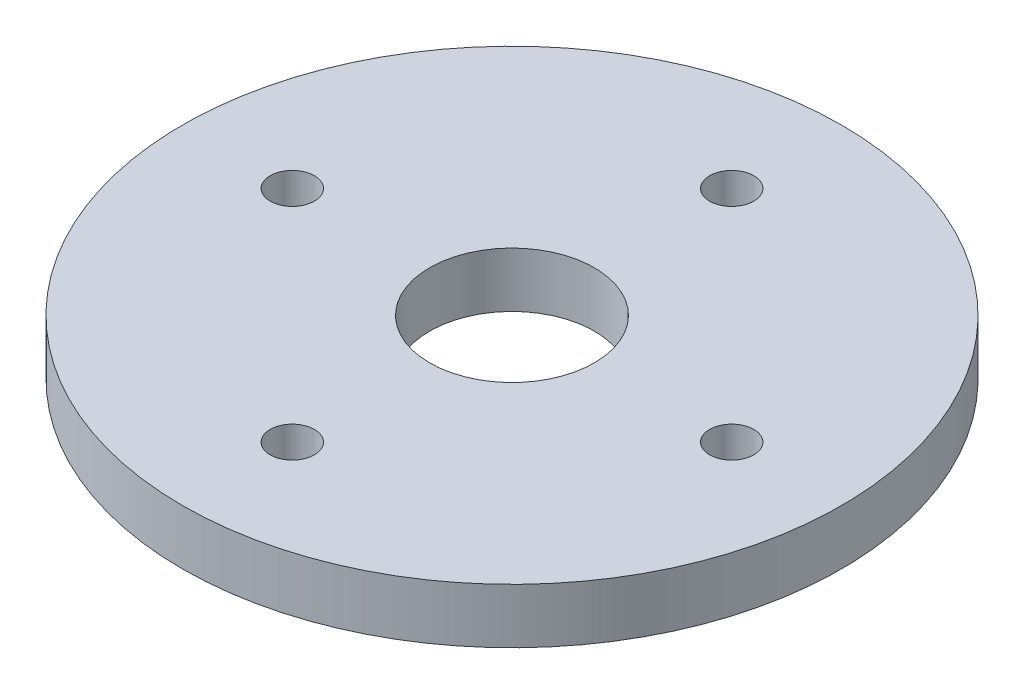
SolidWorks part; units mm, degrees
material "6061 Alloy"
ref_plane "Front" through (0, 0, 0) normal (0, 0, 1) x (1, 0, 0)
ref_plane "Top" through (0, 0, 0) normal (0, 1, 0) x (1, 0, 0)
ref_plane "Right" through (0, 0, 0) normal (1, 0, 0) x (0, 0, -1)
sketch "Sketch1" plane through (0, 0, 0) normal (0, 1, 0) x (1, 0, 0)
  circle A0 centre (0, 0) radius 38.1
  circle A1 centre (0, 0) radius 9.525
  circle A2 centre (0, 0) radius 25.4 construction
  circle A3 centre (0, 25.4) radius 3.175 construction
  circle A4 centre (25.4, 0) radius 3.175 construction
  circle A5 centre (0, -25.4) radius 3.175 construction
  circle A6 centre (-25.4, 0) radius 3.175 construction
  point P15 (39.7821, -3.5967)
  dimension "D1" = 6.35
  dimension "D2" = 19.05
  dimension "D3" = 9.525
  dimension "D4" = 50.8
extrude "Boss-Extrude1" add sketch "Sketch1" along normal blind 6.35
hole_wizard "#10 Clearance Hole1" positions "Sketch2" profile "Sketch3" hole size "#10" standard "ANSI Inch" end condition through all
sketch "Sketch2" plane through (0, 6.35, 0) normal (0, 1, 0) x (1, 0, 0)
  point P0 (-25.4, 0)
  point P3 (0, 25.4)
  point P6 (25.4, 0)
  point P9 (0, -25.4)
sketch "Sketch3" plane through (-25.4, 6.35, 0) normal (1, 0, 0) x (0, 0, 1)
  line L0 (0, 0) -> (0, 6.35)
  line L1 (0, 6.35) -> (2.5527, 6.35)
  line L2 (2.5527, 6.35) -> (2.5527, 0)
  line L5 (2.5527, 0) -> (0, 0)
  line L11 (0, -6.35) -> (0, 107.95) construction
  dimension "Thru Hole Dia." = 5.1054
  dimension "Thru Hole Depth" = 6.35
